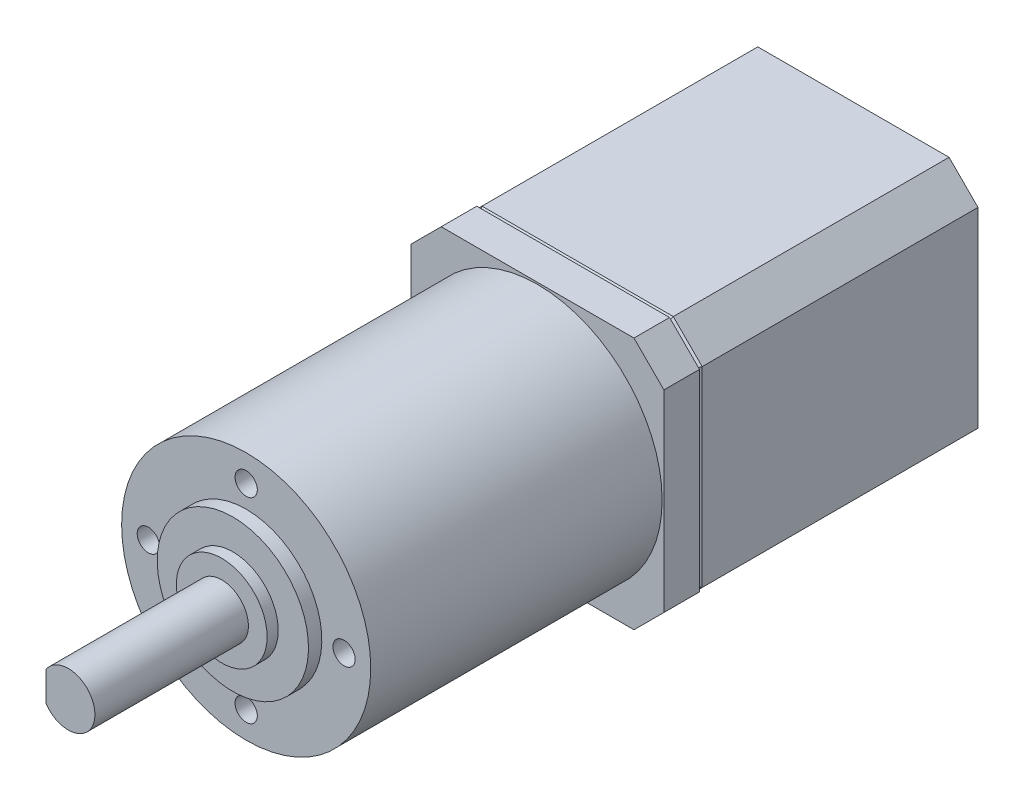
SolidWorks part; units mm, degrees
ref_plane "Front" through (0, 0, 0) normal (0, 0, 1) x (1, 0, 0)
ref_plane "Top" through (0, 0, 0) normal (0, 1, 0) x (1, 0, 0)
ref_plane "Right" through (0, 0, 0) normal (1, 0, 0) x (0, 0, -1)
sketch "Sketch1" plane through (0, 0, 0) normal (0, 0, 1) x (1, 0, 0)
  line L0 (-17.5226, -5.0947) -> (17.4774, -5.0947) construction
  line L1 (10.75, -14) -> (-10.75, -14)
  line L2 (14, -10.75) -> (14, 10.75)
  line L3 (10.75, 14) -> (-10.75, 14)
  line L4 (-14, -10.75) -> (-14, 10.75)
  line L5 (14, -14) -> (-14, 14) construction
  line L6 (14, 14) -> (-14, -14) construction
  line L7 (14, 10.75) -> (10.75, 14)
  line L8 (14, -10.75) -> (10.75, -14)
  line L9 (-10.75, -14) -> (-14, -10.75)
  line L10 (-10.75, 14) -> (-14, 10.75)
  point P0 (0, 0)
  dimension "D1" = 28
  dimension "D2" = 35
  dimension "D3" = 3.25
  dimension "D4" = 3.25
  dimension "D6" = 28
extrude "Boss-Extrude1" add sketch "Sketch1" along normal blind 31.5
ref_plane "Plane1" through (0, 0, 0) normal (1, 0, 0) x (0, 0, -1)
sketch "Sketch2" plane through (0, 0, 0) normal (1, 0, 0) x (0, 0, -1)
  line L0 (-79.6242, -0.2515) -> (-61.6242, -0.2515) construction
  dimension "D1" = 18
sketch "Sketch3" plane through (0, 0, 31.5) normal (0, 0, 1) x (1, 0, 0)
  line L8 (14, 10.75) -> (10.75, 14)
  line L9 (10.75, 14) -> (-10.75, 14)
  line L10 (-10.75, 14) -> (-14, 10.75)
  line L11 (-14, 10.75) -> (-14, -10.75)
  line L12 (-14, -10.75) -> (-10.75, -14)
  line L13 (-10.75, -14) -> (10.75, -14)
  line L14 (10.75, -14) -> (14, -10.75)
  line L15 (14, -10.75) -> (14, 10.75)
  line L16 (14, 10.75) -> (10.75, 14)
  line L17 (10.75, 14) -> (-10.75, 14)
  line L18 (-10.75, 14) -> (-14, 10.75)
  line L19 (-14, 10.75) -> (-14, -10.75)
  line L20 (-14, -10.75) -> (-10.75, -14)
  line L21 (-10.75, -14) -> (10.75, -14)
  line L22 (10.75, -14) -> (14, -10.75)
  line L23 (14, -10.75) -> (14, 10.75)
  dimension "D1" = 0
extrude "Boss-Extrude2" add sketch "Sketch3" along normal blind 4 separate body
chamfer "Chamfer1" distance 0.5 angle 45 8 edges at (0, 14, 31.5) (-12.375, 12.375, 31.5) (-14, 0, 31.5) (-12.375, -12.375, 31.5) (0, -14, 31.5) (12.375, -12.375, 31.5) (14, 0, 31.5) (12.375, 12.375, 31.5)
sketch "Sketch4" plane through (0, 0, 0) normal (1, 0, 0) x (0, 0, -1)
  line L0 (-35.5, 0) -> (-88.25, 0) construction
  line L1 (-35.5, -10.75) -> (-35.5, 10.75) construction
  line L2 (-88.25, 0) -> (-88.25, 3)
  line L3 (-88.25, 3) -> (-69.75, 3)
  line L4 (-69.75, 3) -> (-69.75, 8.5)
  line L5 (-75.9513, 30.812) -> (-39.8513, 30.812) construction
  line L7 (-69.75, 8.5) -> (-68.25, 8.5)
  line L8 (-68.25, 8.5) -> (-68.25, 14)
  line L9 (-68.25, 14) -> (-35.5, 14)
  line L11 (-35.5, 14) -> (-35.5, 0)
  line L12 (-35.5, 0) -> (-88.25, 0)
  dimension "D1" = 32.75
  dimension "D2" = 6
  dimension "D3" = 17
  dimension "D4" = 36.1
  dimension "D5" = 20
  dimension "D6" = 28
  dimension "D8" = 1.5
revolve "Revolve1" add sketch "Sketch4" angle 360 about L0
hole_wizard "M3x0.5 Tapped Hole1" positions "Sketch6" profile "Sketch7" tap size "M3x0.5" standard "ANSI Metric"
sketch "Sketch6" plane through (0, 0, 68.25) normal (0, 0, 1) x (1, 0, 0)
  line L0 (0, 0) -> (0, 11) construction
  line L3 (0, 0) -> (11, 0) construction
  line L6 (0, 0) -> (0, -11) construction
  line L9 (0, 0) -> (-11, 0) construction
  point P0 (0, 11)
  point P11 (11, 0)
  point P17 (0, -11)
  point P23 (-11, 0)
  dimension "D1" = 11
sketch "Sketch7" plane through (0, 11, 68.25) normal (1, 0, 0) x (0, -1, 0)
  line L0 (0, 0) -> (0, 5.7511)
  line L1 (0, 5.7511) -> (1.25, 5)
  line L2 (1.25, 5) -> (1.25, 0)
  line L5 (1.25, 0) -> (0, 0)
  line L10 (0, 5.7511) -> (-1.25, 5) construction
  line L11 (0, -6.35) -> (0, 107.95) construction
  dimension "Tap Drill Dia." = 2.5
  dimension "Tap Drill Depth" = 5
  dimension "Drill Angle" = 118
cosmetic thread "Hole Thread1" parameters "D1"=6, "D2"=3
cosmetic thread "Hole Thread2" parameters "D1"=6, "D2"=3
cosmetic thread "Hole Thread3" parameters "D1"=6, "D2"=3
cosmetic thread "Hole Thread4" parameters "D1"=6, "D2"=3
sketch "Sketch8" plane through (0, 0, 69.75) normal (0, 0, 1) x (1, 0, 0)
  circle A0 centre (0, 0) radius 5.1
  circle A1 centre (0, 0) radius 3 construction
  circle A2 centre (0, 0) radius 3
  dimension "D1" = 10.2
extrude "Boss-Extrude3" add sketch "Sketch8" along normal blind 1.25
sketch "Sketch9" plane through (0, 0, 88.25) normal (0, 0, 1) x (1, 0, 0)
  line L0 (-2.5, 1.6583) -> (-2.5, -1.6583)
  line L1 (-2.5, 0) -> (0, 0) construction
  arc A0 (-2.5, 1.6583) -> (-2.5, -1.6583) centre (0, 0) ccw
  circle A1 centre (0, 0) radius 3 construction
  point P6 (-3, 0)
  dimension "D1" = 0.5
extrude "Cut-Extrude1" cut sketch "Sketch9" against normal blind 15
other "Move Face1" face at (12.375, -12.375, 33.5) face at (0, -14, 33.9) face at (-12.375, -12.375, 33.5) face at (-12.375, 12.375, 33.5) face at (0, 14, 33.9) face at (12.375, 12.375, 33.5) face at (-14, 0, 33.9) face at (14, 0, 33.9) offset 0.2 parameters "D1"=0.2
equation "\"D6@Sketch1\"=\"D1@Sketch1\""
